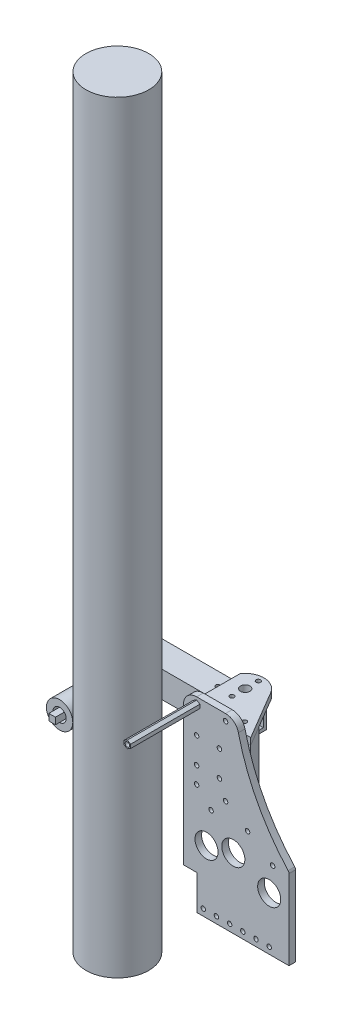
SolidWorks part; units mm, degrees
ref_plane "Front Plane" through (0, 0, 0) normal (0, 0, 1) x (1, 0, 0)
ref_plane "Top Plane" through (0, 0, 0) normal (0, 1, 0) x (1, 0, 0)
ref_plane "Right Plane" through (0, 0, 0) normal (1, 0, 0) x (0, 0, -1)
sketch "Elevation Bar" plane through (0, 0, 0) normal (0, 1, 0) x (1, 0, 0)
  circle A0 centre (0, 0) radius 30.226
  dimension "D1" = 60.452
extrude "Elevation Bar Part" add sketch "Elevation Bar" along normal blind 734.06
sketch "Pole and Drivetrain Pos" plane through (0, 0, 0) normal (0, 0, 1) x (1, 0, 0)
  line L0 (0, 0) -> (172.1794, 0) construction
  line L1 (-30.226, 0) -> (-30.226, 734.06) construction
  line L2 (-30.226, 734.06) -> (30.226, 734.06) construction
  line L3 (30.226, 734.06) -> (30.226, 0) construction
  line L4 (30.226, 0) -> (30.226, 734.06) construction
  line L5 (643.001, 41.275) -> (33.401, 41.275) construction
  line L6 (643.001, 53.975) -> (33.401, 53.975)
  line L7 (643.001, 53.975) -> (643.001, 28.575)
  line L8 (643.001, 28.575) -> (33.401, 28.575)
  line L9 (33.401, 53.975) -> (33.401, 28.575)
  line L10 (-30.226, 93.98) -> (30.226, 93.98) construction
  line L11 (33.2486, 0) -> (-33.2486, 0) construction
  line L12 (30.226, 185.42) -> (-30.226, 185.42) construction
  line L13 (30.226, 276.86) -> (-30.226, 276.86) construction
  line L14 (30.226, 368.3) -> (-30.226, 368.3) construction
  line L15 (30.226, 459.74) -> (-30.226, 459.74) construction
  line L16 (30.226, 551.18) -> (-30.226, 551.18) construction
  line L17 (30.226, 642.62) -> (-30.226, 642.62) construction
  line L18 (30.226, 73.152) -> (750.8896, 73.152) construction
  circle A0 centre (585.851, 41.275) radius 41.275 construction
  circle A1 centre (90.551, 41.275) radius 41.275 construction
  circle A2 centre (338.201, 41.275) radius 41.275 construction
  circle A3 centre (90.551, 41.275) radius 25.4
  point P24 (338.201, 41.275)
  point P28 (34.973, 41.275)
  dimension "D2" = 82.55
  dimension "D5" = 50.8
  dimension "D1" = 609.6
  dimension "D3" = 25.4
  dimension "D6" = 93.98
  dimension "D7" = 185.42
  dimension "D8" = 276.86
  dimension "D9" = 368.3
  dimension "D10" = 459.74
  dimension "D11" = 551.18
  dimension "D12" = 642.62
  dimension "D13" = 73.152
  dimension "D14" = 57.15
  dimension "D4" = 57.15
  dimension "D15" = 6.35
sketch "Driving Wheels Geo" plane through (0, 0, 0) normal (0, 0, 1) x (1, 0, 0)
  line L0 (-30.226, 182.88) -> (-30.226, 101.727) construction
  line L1 (55.626, 101.727) -> (30.226, 101.727) construction
  line L2 (-30.226, 0) -> (-30.226, 734.06) construction
  line L3 (30.226, 734.06) -> (30.226, 0) construction
  line L5 (30.226, 101.727) -> (-30.226, 101.727) construction
  line L6 (-30.226, 182.88) -> (30.226, 101.727) construction
  line L7 (31.8135, 101.727) -> (-30.226, 182.88) construction
  line L8 (30.226, 227.417) -> (203.668, 53.975) construction
  line L9 (-42.926, 195.58) -> (44.8729, 195.58) construction
  line L10 (30.226, 73.152) -> (750.8896, 73.152) construction
  line L11 (643.001, 53.975) -> (33.401, 53.975) construction
  line L14 (-42.926, 170.18) -> (44.8729, 170.18) construction
  line L15 (44.8729, 170.18) -> (44.8729, 195.58) construction
  line L16 (81.026, 28.575) -> (81.026, 257.175) construction
  line L17 (32.1729, 195.58) -> (57.5729, 195.58) construction
  line L18 (32.1729, 195.58) -> (32.1729, 170.18) construction
  line L19 (32.1729, 170.18) -> (57.5729, 170.18) construction
  line L20 (57.5729, 195.58) -> (57.5729, 170.18) construction
  line L21 (32.1729, 195.58) -> (57.5729, 170.18) construction
  line L22 (32.1729, 170.18) -> (57.5729, 195.58) construction
  line L23 (643.001, 28.575) -> (33.401, 28.575) construction
  line L24 (284.226, 257.175) -> (81.026, 257.175) construction
  line L25 (284.226, 257.175) -> (284.226, 53.975) construction
  line L26 (81.026, 257.175) -> (30.226, 257.175) construction
  circle A1 centre (55.626, 101.727) radius 25.4
  circle A3 centre (-42.926, 182.88) radius 12.7
  circle A4 centre (81.026, 104.775) radius 50.8 construction
  circle A5 centre (55.626, 101.727) radius 23.8125 construction
  circle A7 centre (284.226, 257.175) radius 203.2 construction
  point P28 (44.8729, 182.88)
  dimension "D1" = 50.8
  dimension "D2" = 1.5875
  dimension "D3" = 52.603
  dimension "D4" = 3.175
  dimension "D5" = 182.88
  dimension "D8" = 101.6
  dimension "D6" = 25.4
  dimension "D13" = 3.175
  dimension "D14" = 50.8
  dimension "D16" = 406.4
  dimension "D7" = 81.153
  dimension "D9" = 45
  dimension "D10" = 53.317
  dimension "D11" = 25.4
  dimension "D12" = 47.752
ref_plane "Plane1" through (0, 182.88, 0) normal (0, 1, 0) x (1, 0, 0)
sketch "Clamp Geo" plane through (0, 182.88, 0) normal (0, 1, 0) x (1, 0, 0)
  line L0 (-42.926, -19.8438) -> (-42.926, 87.3125) construction
  line L3 (33.401, 228.6) -> (33.401, -228.6) construction
  line L4 (56.3149, 61.9125) -> (-49.276, 61.9125)
  line L5 (56.3149, 61.9125) -> (56.3149, 87.3125)
  line L6 (56.3149, 87.3125) -> (-49.276, 87.3125)
  line L7 (-49.276, 61.9125) -> (-49.276, 87.3125)
  line L10 (-46.101, 87.3125) -> (-39.751, 87.3125)
  line L11 (-46.101, 87.3125) -> (-46.101, -19.8438)
  line L12 (-46.101, -19.8438) -> (-39.751, -19.8438)
  line L13 (-39.751, 87.3125) -> (-39.751, -19.8438)
  line L14 (-55.626, 12.7) -> (-30.226, 12.7) construction
  line L15 (-55.626, 12.7) -> (-55.626, -12.7) construction
  line L16 (-55.626, -12.7) -> (-30.226, -12.7) construction
  line L17 (-30.226, 12.7) -> (-30.226, -12.7) construction
  line L18 (-55.626, 12.7) -> (-30.226, -12.7) construction
  line L19 (-55.626, -12.7) -> (-30.226, 12.7) construction
  line L20 (0, -30.226) -> (0, 30.226) construction
  line L21 (-30.226, 0) -> (30.226, 0) construction
  line L22 (-46.101, 80.9625) -> (-42.926, 80.9625) construction
  line L23 (-39.751, 74.6125) -> (-46.101, 74.6125)
  line L24 (-46.101, 74.6125) -> (-46.101, 87.3125) construction
  line L25 (-39.751, 61.9125) -> (-39.751, 87.3125) construction
  line L26 (56.3149, 74.6125) -> (48.3774, 74.6125) construction
  line L27 (36.576, 57.1119) -> (36.576, 61.9125) construction
  line L28 (33.401, 61.9125) -> (39.751, 61.9125)
  line L29 (33.401, 61.9125) -> (33.401, 57.1119)
  line L30 (33.401, 57.1119) -> (39.751, 57.1119)
  line L31 (39.751, 61.9125) -> (39.751, 57.1119)
  circle A0 centre (0, 0) radius 30.226 construction
  circle A3 centre (-42.926, 80.9625) radius 1.8288
  circle A5 centre (-42.926, 68.2625) radius 1.8288
  circle A6 centre (48.3774, 74.6125) radius 4.7625
  circle A7 centre (48.3774, 74.6125) radius 14.9764 construction
  point P14 (-42.926, 0)
  point P32 (-39.751, 74.6125)
  point P34 (-46.101, 74.6125)
  point P36 (-42.926, 74.6125)
  point P42 (56.3149, 74.6125)
  point P50 (0, 0)
  dimension "D1" = 60.452
  dimension "D4" = 61.9125
  dimension "D7" = 3.6576
  dimension "D8" = 3.175
  dimension "D10" = 9.525
  dimension "D11" = 3.175
  dimension "D12" = 4.8006
  dimension "D2" = 457.2
  dimension "D3" = 25.4
  dimension "D5" = 6.35
  dimension "D6" = 25.4
  dimension "D9" = 105.5909
  dimension "D13" = 7.1437
  dimension "D14" = 6.35
extrude "Boss-Extrude1" add sketch "Clamp Geo" along normal blind 12.7 and the other way blind 12.7 separate body contours L6 L13 L4 L5 A6 | L11 L6 L7 L4 | L13 L23 L11 L4 A5 | L23 L13 L6 L11 A3 region at (7.0759, 182.88, -74.6125) region at (-39.893, 182.88, -80.9625) region at (-42.926, 182.88, -62.0545) region at (-47.6885, 182.88, -74.6125)
sketch "Locked Setting Geo" plane through (0, 182.88, 0) normal (0, 1, 0) x (1, 0, 0)
  line L0 (37.1358, 206.7277) -> (116.0692, 134.2573) construction
  line L1 (34.9193, 74.038) -> (106.3312, 151.8184)
  line L2 (34.9193, 74.038) -> (48.9519, 61.1544)
  line L3 (48.9519, 61.1544) -> (120.3638, 138.9348)
  line L4 (106.3312, 151.8184) -> (120.3638, 138.9348)
  line L5 (118.2165, 136.596) -> (113.922, 131.9185)
  line L6 (118.2165, 136.596) -> (39.283, 209.0665)
  line L7 (39.283, 209.0665) -> (34.9885, 204.389)
  line L8 (113.922, 131.9185) -> (34.9885, 204.389)
  line L9 (72.036, 191.926) -> (54.8578, 173.2158) construction
  line L10 (72.036, 191.926) -> (53.3259, 209.1042) construction
  line L11 (53.3259, 209.1042) -> (36.1477, 190.394) construction
  line L12 (54.8578, 173.2158) -> (36.1477, 190.394) construction
  line L13 (72.036, 191.926) -> (36.1477, 190.394) construction
  line L14 (53.3259, 209.1042) -> (54.8578, 173.2158) construction
  line L15 (39.751, 61.9125) -> (39.751, 57.1119) construction
  line L16 (47.1953, 87.4087) -> (28.4851, 104.5869)
  line L17 (114.7084, 139.8169) -> (112.5611, 137.4782) construction
  line L18 (106.9057, 138.3603) -> (111.2002, 143.0379)
  line L19 (111.2002, 143.0379) -> (118.2165, 136.596) construction
  line L20 (99.8893, 144.8021) -> (113.922, 131.9185) construction
  line L21 (41.9356, 67.5962) -> (48.3774, 74.6125) construction
  line L22 (56.3149, 87.3125) -> (-49.276, 87.3125) construction
  line L23 (-46.101, 87.3125) -> (-46.101, -19.8438) construction
  line L24 (33.401, 228.6) -> (33.401, -228.6) construction
  line L25 (28.4851, 104.5869) -> (32.7797, 109.2645)
  line L26 (32.7797, 109.2645) -> (51.4898, 92.0863)
  circle A1 centre (112.5611, 137.4782) radius 1.8288
  circle A2 centre (105.5448, 143.92) radius 1.8288
  circle A3 centre (48.3774, 74.6125) radius 6.35
  point P0 (-42.926, 74.6125)
  point P9 (-42.926, 0)
  point P10 (54.0919, 191.16)
  point P28 (106.9057, 138.3603)
  point P30 (111.2002, 143.0379)
  point P32 (109.0529, 140.6991)
  point P36 (41.9356, 67.5962)
  point P40 (48.3774, 74.6125)
  dimension "D15" = 6.35
  dimension "D6" = 3.6576
  dimension "D9" = 12.7
  dimension "D2" = 19.05
  dimension "D4" = 6.35
  dimension "D5" = 25.4
  dimension "D7" = 3.175
  dimension "D8" = 105.5909
  dimension "D10" = 3.175
  dimension "D3" = 1.5875
  dimension "D12" = 86.9628
  dimension "D11" = 74.6125
  dimension "D13" = 74.6125
  dimension "D14" = 8.6264
  dimension "D16" = 25.4
  dimension "D17" = 8.6264
sketch "Sketch2" plane through (-49.276, 0, 0) normal (-1, 0, 0) x (0, 0, 1)
  line L0 (-74.6125, 195.58) -> (-74.6125, 170.18) construction
  line L1 (-61.9125, 195.58) -> (-87.3125, 195.58) construction
  line L2 (-61.9125, 170.18) -> (-87.3125, 170.18) construction
  line L3 (-61.9125, 170.18) -> (-61.9125, 195.58) construction
  line L4 (-84.1375, 173.355) -> (-65.0875, 173.355)
  line L5 (-84.1375, 173.355) -> (-84.1375, 192.405)
  line L6 (-84.1375, 192.405) -> (-65.0875, 192.405)
  line L7 (-65.0875, 173.355) -> (-65.0875, 192.405)
  line L8 (-84.1375, 173.355) -> (-65.0875, 192.405) construction
  line L9 (-84.1375, 192.405) -> (-65.0875, 173.355) construction
  point P6 (-74.6125, 182.88)
  dimension "D1" = 3.175
  dimension "D2" = 3.175
extrude "Cut-Extrude2" cut sketch "Sketch2" against normal up to surface (105.5909 mm away) up to face at (56.3149, 182.88, -74.6125)
sketch "Sketch3" plane through (0, 0, -87.3125) normal (0, 0, -1) x (-1, 0, 0)
  line L2 (39.7129, 179.6669) -> (46.1391, 179.6669) construction
  line L3 (39.7129, 179.6669) -> (39.7129, 186.0931) construction
  line L4 (39.7129, 186.0931) -> (46.1391, 186.0931) construction
  line L5 (46.1391, 179.6669) -> (46.1391, 186.0931) construction
  line L6 (39.7129, 179.6669) -> (46.1391, 186.0931) construction
  line L7 (39.7129, 186.0931) -> (46.1391, 179.6669) construction
  circle A1 centre (42.926, 182.88) radius 4.544
  point P0 (42.926, 182.88)
  point P1 (42.926, 182.88)
  dimension "D1" = 6.4262
extrude "Cut-Extrude3" cut sketch "Sketch3" against normal up to surface (25.4 mm away) up to face at (3.5195, 182.88, -61.9125)
extrude "Boss-Extrude2" add sketch "Clamp Geo<3>" along normal blind 3.175 and the other way blind 3.175 separate body contours L13 L4 L11 L12 | L13 L23 L11 L4 A5 | L23 L13 L6 L11 A3 region at (-39.893, 182.88, -80.9625) region at (-42.926, 182.88, -21.0344) region at (-42.926, 182.88, -62.0545)
sketch "Clamp Geo<3>" plane through (0, 182.88, 0) normal (0, 1, 0) x (1, 0, 0) same geometry as "Clamp Geo"
sketch "Custom Driven Flywheel" plane through (0, 0, 0) normal (0, 0, 1) x (1, 0, 0)
  circle A0 centre (-42.926, 182.88) radius 12.7 construction
  circle A1 centre (-42.926, 182.88) radius 12.7
  circle A2 centre (-42.926, 182.88) radius 6.35
  dimension "D1" = 12.7
extrude "Boss-Extrude3" add sketch "Custom Driven Flywheel" along normal blind 12.7 and the other way blind 25.4 separate body
sketch "Sketch8" plane through (0, 173.355, 0) normal (0, 1, 0) x (1, 0, 0)
  line L0 (-42.926, 84.1375) -> (-42.926, 65.0875) construction
  line L5 (-36.576, 74.6125) -> (-42.926, 74.6125) construction
  line L6 (-42.926, 74.6125) -> (-49.276, 74.6125) construction
  line L11 (56.3149, 65.0875) -> (-49.276, 65.0875) construction
  line L12 (56.3149, 84.1375) -> (-49.276, 84.1375) construction
  line L13 (56.3149, 65.0875) -> (-49.276, 65.0875) construction
  line L14 (56.3149, 84.1375) -> (-49.276, 84.1375) construction
  line L15 (-49.276, 84.1375) -> (-49.276, 65.0875) construction
  line L17 (-49.276, 65.3415) -> (-36.576, 65.3415)
  line L18 (-49.276, 65.3415) -> (-49.276, 83.8835)
  line L19 (-49.276, 83.8835) -> (-36.576, 83.8835)
  line L20 (-36.576, 65.3415) -> (-36.576, 83.8835)
  line L21 (-49.276, 65.3415) -> (-36.576, 83.8835) construction
  line L22 (-49.276, 83.8835) -> (-36.576, 65.3415) construction
  circle A0 centre (-42.926, 80.9625) radius 1.8288 construction
  circle A1 centre (-42.926, 80.9625) radius 1.8288 construction
  circle A2 centre (-42.926, 68.2625) radius 1.8288 construction
  circle A3 centre (-42.926, 80.9625) radius 1.8288
  circle A4 centre (-42.926, 68.2625) radius 1.8288
  dimension "D1" = 0.254
extrude "Boss-Extrude5" add sketch "Sketch8" along normal up to surface (9.525 mm away) separate body up to plane "Plane1"
sketch "Sketch10" plane through (0, 182.88, 0) normal (0, 1, 0) x (1, 0, 0)
  line L0 (-36.576, 83.8835) -> (-49.276, 83.8835) construction
  line L8 (-39.751, 65.3415) -> (-46.101, 65.3415)
  line L9 (-39.751, 65.3415) -> (-39.751, 83.8835)
  line L10 (-39.751, 83.8835) -> (-46.101, 83.8835)
  line L11 (-46.101, 65.3415) -> (-46.101, 83.8835)
  line L12 (-39.751, 65.3415) -> (-46.101, 83.8835) construction
  line L13 (-39.751, 83.8835) -> (-46.101, 65.3415) construction
  circle A0 centre (-42.926, 68.2625) radius 1.8288 construction
  circle A1 centre (-42.926, 80.9625) radius 1.8288 construction
  circle A2 centre (-42.926, 68.2625) radius 1.8288
  circle A3 centre (-42.926, 80.9625) radius 1.8288
  point P0 (-42.926, 74.6125)
  dimension "D1" = 6.35
extrude "Cut-Extrude5" cut sketch "Sketch10" against normal blind 3.175
ref_plane "Plane2" through (0, 0, 210.82) normal (0, 0, 1) x (1, 0, 0)
ref_plane "Plane3" through (0, 0, 166.37) normal (0, 0, 1) x (1, 0, 0)
sketch "Sketch12" plane through (0, 0, 166.37) normal (0, 0, 1) x (1, 0, 0)
  line L0 (643.001, 41.275) -> (33.401, 41.275) construction
  line L1 (643.001, 41.275) -> (33.401, 41.275) construction
  line L2 (90.551, 41.275) -> (103.251, 41.275) construction
  line L3 (115.951, 41.275) -> (115.951, 92.4703) construction
  circle A0 centre (90.551, 41.275) radius 25.4 construction
  circle A1 centre (90.551, 41.275) radius 25.4
  circle A2 centre (55.626, 101.727) radius 17.78
  circle A4 centre (81.4092, 108.5474) radius 8.89
  circle A5 centre (135.001, 41.275) radius 19.05
  circle A7 centre (81.4092, 108.5474) radius 25.4
  circle A8 centre (115.951, 92.4703) radius 12.7
  circle A9 centre (115.951, 92.4703) radius 31.75
  circle A10 centre (90.551, 41.275) radius 3.175 construction
  circle A11 centre (103.251, 41.275) radius 3.175 construction
  circle A12 centre (115.951, 41.275) radius 3.175 construction
  circle A13 centre (128.651, 41.275) radius 3.175 construction
  circle A14 centre (141.351, 41.275) radius 3.175 construction
  circle A15 centre (154.051, 41.275) radius 3.175 construction
  circle A16 centre (166.751, 41.275) radius 3.175 construction
  circle A17 centre (179.451, 41.275) radius 3.175 construction
  circle A18 centre (192.151, 41.275) radius 3.175 construction
  circle A19 centre (204.851, 41.275) radius 3.175 construction
  point P0 (78.4034, 98.9347)
  point P3 (55.626, 101.727)
  dimension "D2" = 17.78
  dimension "D3" = 63.5
  dimension "D4" = 38.1
  dimension "D5" = 50.8
  dimension "D6" = 25.4
  dimension "D7" = 35.56
  dimension "D8" = 6.35
  dimension "D10" = 12.7
  dimension "D9" = 10
sketch "Sketch13" plane through (0, 0, 210.82) normal (0, 0, 1) x (1, 0, 0)
  line L0 (115.951, 79.7703) -> (115.951, 105.1703) construction
  line L2 (96.901, 79.7703) -> (96.901, 105.1703)
  line L4 (160.401, 79.7703) -> (160.401, 105.1703)
  line L5 (154.051, 92.4703) -> (154.051, 41.275) construction
  line L6 (115.951, 92.4703) -> (160.401, 92.4703) construction
  line L7 (96.901, 92.4703) -> (115.951, 92.4703) construction
  line L8 (96.901, 105.1703) -> (115.951, 105.1703)
  line L9 (96.901, 79.7703) -> (115.951, 79.7703)
  line L10 (115.951, 105.1703) -> (160.401, 105.1703)
  line L11 (160.401, 79.7703) -> (115.951, 79.7703)
  circle A0 centre (115.951, 92.4703) radius 3.175 construction
  circle A1 centre (103.251, 92.4703) radius 3.175 construction
  circle A2 centre (154.051, 92.4703) radius 3.175 construction
  point P0 (115.951, 92.4703)
  dimension "D2" = 6.35
  dimension "D3" = 6.35
  dimension "D6" = 6.35
  dimension "D1" = 25.4
  dimension "D4" = 12.7
  dimension "D5" = 6.35
ref_plane "Plane5" through (0, 0, 146.177) normal (0, 0, 1) x (1, 0, 0)
sketch "Sketch15" plane through (0, 0, 146.177) normal (0, 0, 1) x (1, 0, 0)
  line L0 (96.901, 79.7703) -> (115.951, 79.7703) construction
  line L1 (160.401, 79.7703) -> (115.951, 79.7703) construction
  line L2 (160.401, 79.7703) -> (160.401, 105.1703) construction
  line L3 (115.951, 105.1703) -> (160.401, 105.1703) construction
  line L4 (96.901, 105.1703) -> (115.951, 105.1703) construction
  line L5 (96.901, 79.7703) -> (96.901, 105.1703) construction
  line L6 (96.901, 79.7703) -> (115.951, 79.7703)
  line L7 (160.401, 79.7703) -> (115.951, 79.7703)
  line L8 (160.401, 79.7703) -> (160.401, 105.1703)
  line L9 (115.951, 105.1703) -> (160.401, 105.1703)
  line L10 (96.901, 105.1703) -> (115.951, 105.1703)
  line L11 (96.901, 79.7703) -> (96.901, 105.1703)
  line L12 (96.901, 28.575) -> (115.951, 28.575)
  line L13 (160.401, 28.575) -> (115.951, 28.575)
  line L14 (160.401, 28.575) -> (160.401, 53.975)
  line L15 (115.951, 53.975) -> (160.401, 53.975)
  line L16 (96.901, 53.975) -> (115.951, 53.975)
  line L17 (96.901, 28.575) -> (96.901, 53.975)
  line L18 (160.401, 28.575) -> (96.901, 53.975) construction
  line L19 (115.951, 53.975) -> (115.951, 28.575) construction
  line L20 (160.401, 41.275) -> (96.901, 41.275) construction
  circle A0 centre (115.951, 92.4703) radius 3.175 construction
  circle A1 centre (115.951, 92.4703) radius 3.175
  circle A2 centre (115.951, 41.275) radius 3.175 construction
  dimension "D5" = 6.35
  dimension "D1" = 68.3916
  dimension "D2" = 68.3916
  dimension "D3" = 19.05
  dimension "D4" = 25.4
ref_plane "Plane6" through (0, 53.975, 0) normal (0, 1, 0) x (1, 0, 0)
ref_plane "Plane9" through (0, 74.6125, 0) normal (0, 1, 0) x (1, 0, 0)
sketch "Sketch16" plane through (0, 74.6125, 0) normal (0, 1, 0) x (1, 0, 0)
  line L0 (33.401, -127) -> (33.401, 127)
  line L1 (39.751, 120.65) -> (39.751, 107.95) construction
  line L2 (33.401, 127) -> (46.101, 127)
  line L3 (33.401, 127) -> (33.401, -127)
  line L4 (33.401, -127) -> (46.101, -127)
  line L5 (46.101, 127) -> (46.101, -127)
  line L6 (39.751, 120.65) -> (39.751, 127) construction
  line L7 (141.351, -166.37) -> (141.351, -127) construction
  line L8 (643.001, 0) -> (33.401, 0) construction
  line L9 (135.001, 127) -> (147.701, 127)
  line L14 (135.001, 127) -> (135.001, -127)
  line L15 (135.001, -127) -> (147.701, -127)
  line L16 (147.701, 127) -> (147.701, -127)
  line L17 (135.001, 127) -> (147.701, -127) construction
  line L18 (135.001, -127) -> (147.701, 127) construction
  line L19 (141.351, -120.65) -> (141.351, -107.95) construction
  line L20 (141.351, -127) -> (141.351, -120.65) construction
  circle A0 centre (39.751, 120.65) radius 3.175
  circle A1 centre (39.751, 107.95) radius 3.175
  circle A2 centre (39.751, 95.25) radius 3.175
  circle A3 centre (39.751, 82.55) radius 3.175
  circle A4 centre (39.751, 69.85) radius 3.175
  circle A5 centre (39.751, 57.15) radius 3.175
  circle A6 centre (39.751, 44.45) radius 3.175
  circle A7 centre (39.751, 31.75) radius 3.175
  circle A8 centre (39.751, 19.05) radius 3.175
  circle A9 centre (39.751, 6.35) radius 3.175
  circle A10 centre (39.751, -6.35) radius 3.175
  circle A11 centre (39.751, -19.05) radius 3.175
  circle A12 centre (39.751, -31.75) radius 3.175
  circle A13 centre (39.751, -44.45) radius 3.175
  circle A14 centre (39.751, -57.15) radius 3.175
  circle A15 centre (39.751, -69.85) radius 3.175
  circle A16 centre (39.751, -82.55) radius 3.175
  circle A17 centre (39.751, -95.25) radius 3.175
  circle A18 centre (39.751, -107.95) radius 3.175
  circle A19 centre (39.751, -120.65) radius 3.175
  circle A40 centre (141.351, -120.65) radius 3.175
  circle A41 centre (141.351, -107.95) radius 3.175
  circle A42 centre (141.351, -95.25) radius 3.175
  circle A43 centre (141.351, -82.55) radius 3.175
  circle A44 centre (141.351, -69.85) radius 3.175
  circle A45 centre (141.351, -57.15) radius 3.175
  circle A46 centre (141.351, -44.45) radius 3.175
  circle A47 centre (141.351, -31.75) radius 3.175
  circle A48 centre (141.351, -19.05) radius 3.175
  circle A49 centre (141.351, -6.35) radius 3.175
  circle A50 centre (141.351, 6.35) radius 3.175
  circle A51 centre (141.351, 19.05) radius 3.175
  circle A52 centre (141.351, 31.75) radius 3.175
  circle A53 centre (141.351, 44.45) radius 3.175
  circle A54 centre (141.351, 57.15) radius 3.175
  circle A55 centre (141.351, 69.85) radius 3.175
  circle A56 centre (141.351, 82.55) radius 3.175
  circle A57 centre (141.351, 95.25) radius 3.175
  circle A58 centre (141.351, 107.95) radius 3.175
  circle A59 centre (141.351, 120.65) radius 3.175
  point P3 (33.401, 0)
  point P9 (141.351, -166.37)
  point P51 (141.351, 0)
  point P60 (0, 0)
  dimension "D3" = 6.35
  dimension "D1" = 254
  dimension "D2" = 12.7
  dimension "D4" = 6.35
  dimension "D6" = 12.7
  dimension "D10" = 6.35
  dimension "D12" = 12.7
  dimension "D5" = 20
  dimension "D11" = 20
sketch "Sketch18" plane through (0, 53.975, 0) normal (0, 1, 0) x (1, 0, 0)
  line L0 (33.401, -36.5125) -> (147.701, -36.5125)
  line L3 (643.001, 0) -> (33.401, 0) construction
  line L4 (33.401, -49.2125) -> (147.701, -49.2125)
  line L5 (33.401, -36.5125) -> (33.401, -49.2125)
  line L6 (147.701, -36.5125) -> (147.701, -49.2125)
  line L7 (33.401, -42.8625) -> (147.701, -42.8625) construction
  line L8 (39.751, -42.8625) -> (52.451, -42.8625) construction
  line L9 (-403.733, 0) -> (403.733, 0) construction
  line L10 (39.751, 42.8625) -> (52.451, 42.8625) construction
  line L11 (33.401, 42.8625) -> (147.701, 42.8625) construction
  line L12 (147.701, 36.5125) -> (147.701, 49.2125)
  line L13 (33.401, 36.5125) -> (33.401, 49.2125)
  line L14 (33.401, 49.2125) -> (147.701, 49.2125)
  line L15 (33.401, 36.5125) -> (147.701, 36.5125)
  line L16 (33.401, 228.6) -> (33.401, -228.6) construction
  line L17 (147.701, 127) -> (147.701, -127) construction
  circle A0 centre (39.751, -42.8625) radius 3.175
  circle A1 centre (52.451, -42.8625) radius 3.175
  circle A2 centre (65.151, -42.8625) radius 3.175
  circle A3 centre (77.851, -42.8625) radius 3.175
  circle A4 centre (90.551, -42.8625) radius 3.175
  circle A5 centre (103.251, -42.8625) radius 3.175
  circle A6 centre (115.951, -42.8625) radius 3.175
  circle A7 centre (115.951, 42.8625) radius 3.175
  circle A8 centre (103.251, 42.8625) radius 3.175
  circle A9 centre (90.551, 42.8625) radius 3.175
  circle A10 centre (77.851, 42.8625) radius 3.175
  circle A11 centre (65.151, 42.8625) radius 3.175
  circle A12 centre (52.451, 42.8625) radius 3.175
  circle A13 centre (39.751, 42.8625) radius 3.175
  circle A14 centre (128.651, -42.8625) radius 3.175
  circle A15 centre (141.351, -42.8625) radius 3.175
  dimension "D4" = 6.35
  dimension "D1" = 36.5125
  dimension "D2" = 12.7
  dimension "D3" = 6.35
  dimension "D6" = 12.7
  dimension "D8" = 12.7
  dimension "D5" = 7
  dimension "D7" = 3
ref_plane "Plane7" through (0, 0, -36.5125) normal (0, 0, 1) x (1, 0, 0)
sketch "Sketch17" plane through (0, 0, -36.5125) normal (0, 0, 1) x (1, 0, 0)
  line L2 (135.001, 118.0172) -> (135.001, 73.152)
  line L9 (33.401, 53.975) -> (147.701, 53.975) construction
  line L10 (46.355, 74.6125) -> (46.355, 41.275)
  line L11 (46.355, 41.275) -> (135.001, 41.275)
  line L13 (135.001, 73.152) -> (135.001, 41.275)
  line L14 (55.626, 101.727) -> (55.626, 41.275) construction
  line L15 (46.101, 214.63) -> (46.101, 147.955) construction
  line L17 (33.401, 74.6125) -> (33.401, 208.28)
  line L20 (46.355, 74.6125) -> (33.401, 74.6125)
  line L23 (46.101, 220.98) -> (46.101, 214.63) construction
  line L24 (46.101, 214.63) -> (73.9355, 214.63) construction
  line L25 (73.9355, 220.98) -> (73.9355, 214.63) construction
  line L27 (33.401, 160.02) -> (33.401, 136.2126) construction
  line L30 (56.3149, 170.18) -> (-49.276, 170.18) construction
  line L31 (73.9355, 214.63) -> (73.9355, 147.955) construction
  line L32 (46.101, 147.955) -> (73.9355, 147.955) construction
  line L33 (81.4092, 108.5474) -> (134.1706, 120.1581) construction
  line L35 (46.101, 220.98) -> (73.9355, 220.98)
  line L36 (60.0183, 214.63) -> (60.0183, 220.98) construction
  line L37 (56.3149, 195.58) -> (-49.276, 195.58) construction
  line L38 (60.0183, 147.955) -> (60.0183, 118.9559) construction
  line L39 (73.9355, 147.955) -> (119.2867, 116.8828) construction
  circle A0 centre (55.626, 101.727) radius 11.1125
  circle A1 centre (81.4092, 108.5474) radius 11.1125
  circle A2 centre (115.951, 92.4703) radius 11.1125
  circle A6 centre (284.226, 257.175) radius 203.2 construction
  arc A7 (86.3055, 211.1562) -> (134.1706, 120.1581) centre (284.226, 257.175) ccw
  arc A9 (135.001, 118.0172) -> (134.1706, 120.1581) centre (131.826, 118.0172) ccw
  arc A10 (86.3055, 211.1562) -> (73.9355, 220.98) centre (73.9355, 208.28) ccw
  arc A11 (33.401, 208.28) -> (46.101, 220.98) centre (46.101, 208.28) cw
  circle A12 centre (46.101, 214.63) radius 2.1527
  circle A13 centre (73.9355, 214.63) radius 2.1527
  circle A21 centre (119.2867, 116.8828) radius 2.1527
  circle A23 centre (46.101, 147.955) radius 2.1527
  circle A24 centre (73.9355, 147.955) radius 2.1527
  circle A25 centre (55.626, 101.727) radius 17.78 construction
  circle A26 centre (60.0183, 133.4555) radius 2.1527
  circle A27 centre (95.0982, 133.4555) radius 2.1526
  point P22 (0, 0)
  point P25 (135.001, 119.2542)
  point P26 (0, 0)
  point P27 (0, 0)
  point P33 (134.6729, 73.152)
  point P55 (0, 0)
  point P56 (33.3012, 75.6194)
  point P57 (33.4967, 72.7702)
  point P58 (33.5821, 75.0431)
  point P59 (33.7233, 74.0007)
  point P60 (33.702, 73.7674)
  point P61 (0, 0)
  point P62 (46.101, 147.955)
  point P65 (91.2977, 135.194)
  point P66 (0, 0)
  point P70 (135.8375, 41.275)
  dimension "D1" = 22.225
  dimension "D2" = 25.4
  dimension "D6" = 12.7
  dimension "D7" = 3.175
  dimension "D9" = 4.3053
  dimension "D13" = 15.24
  dimension "D3" = 12.954
  dimension "D4" = 12.7
  dimension "D5" = 88.646
  dimension "D8" = 6.35
  dimension "D10" = 22.225
extrude "Boss-Extrude6" add sketch "Sketch17" along normal blind 6.35 separate body
sketch "Sketch19" plane through (0, 0, 0) normal (0, 0, 1) x (1, 0, 0)
  line L0 (39.751, 47.625) -> (115.951, 47.625) construction
  line L1 (39.751, 41.275) -> (39.751, 53.975) construction
  line L2 (643.001, 41.275) -> (33.401, 41.275) construction
  line L3 (643.001, 53.975) -> (33.401, 53.975) construction
  line L4 (39.751, 47.625) -> (52.451, 47.625) construction
  circle A0 centre (39.751, 47.625) radius 2.1527
  circle A1 centre (52.451, 47.625) radius 2.1527
  circle A2 centre (65.151, 47.625) radius 2.1527
  circle A3 centre (77.851, 47.625) radius 2.1527
  circle A4 centre (90.551, 47.625) radius 2.1527
  circle A5 centre (103.251, 47.625) radius 2.1527
  circle A6 centre (115.951, 47.625) radius 2.1527
  dimension "D2" = 4.3053
  dimension "D1" = 6.35
  dimension "D4" = 12.7
  dimension "D3" = 7
sketch "Sketch22" plane through (0, 53.975, 0) normal (0, 1, 0) x (1, 0, 0)
  line L0 (-52.7651, -82.55) -> (244.2686, -82.55) construction
  line L1 (-403.733, 0) -> (403.733, 0) construction
  line L2 (-52.7651, 82.55) -> (244.2686, 82.55) construction
  dimension "D1" = 165.1
extrude "Cut-Extrude6" cut sketch "Sketch19" against normal up to surface (36.5125 mm away) up to face at (97.2508, 133.4555, -36.5125)
ref_plane "Plane8" through (0, 200.3425, 0) normal (0, 1, 0) x (1, 0, 0)
sketch "Sketch23" plane through (0, 200.3425, 0) normal (0, 1, 0) x (1, 0, 0)
  line L0 (33.401, 84.6476) -> (33.401, 36.5125)
  line L1 (54.6037, 36.5125) -> (50.2984, 36.5125) construction
  line L2 (33.401, 36.5125) -> (91.821, 36.5125)
  line L3 (91.821, 36.5125) -> (63.8994, 83.7813)
  line L4 (33.401, 57.0961) -> (79.6623, 57.0961) construction
  line L5 (56.5317, 57.0961) -> (56.5317, 36.5125) construction
  line L6 (86.3055, 36.5125) -> (134.1706, 36.5125) construction
  line L7 (56.5317, 46.8043) -> (33.401, 46.8043) construction
  line L8 (35.2696, 74.6125) -> (48.4608, 74.6125) construction
  line L9 (56.5317, 46.8043) -> (75.5817, 46.8043) construction
  line L10 (48.3774, 74.6125) -> (48.3774, 87.3125) construction
  line L11 (33.401, 228.6) -> (33.401, -228.6) construction
  circle A0 centre (48.3774, 74.6125) radius 14.9764 construction
  circle A4 centre (56.5317, 46.8043) radius 2.1527
  circle A7 centre (48.3774, 74.6125) radius 4.5466
  circle A8 centre (75.5817, 46.8043) radius 2.1527
  circle A9 centre (48.3774, 87.3125) radius 2.1527
  circle A10 centre (48.3774, 61.9125) radius 2.1527
  arc A11 (33.401, 64.5774) -> (33.401, 84.6476) centre (48.3774, 74.6125) ccw
  point P27 (62.8176, 83.2089)
  point P28 (0, 0)
  point P29 (0, 0)
  point P32 (27.051, 84.5816)
  dimension "D4" = 4.3053
  dimension "D3" = 9.0932
  dimension "D2" = 2.54
  dimension "D6" = 4.3053
  dimension "D8" = 3.175
  dimension "D1" = 58.42
  dimension "D5" = 19.05
  dimension "D7" = 12.7
extrude "Boss-Extrude7" add sketch "Sketch23" along normal blind 6.35 separate body contours A11 L0 L2 L3 A4 | A11 L0 | A11 | A11 | A11 | A11 region at (48.8754, 200.3425, -92.1443) region at (60.4886, 200.3425, -49.5269)
sketch "Sketch25" plane through (0, 200.3425, 0) normal (0, -1, 0) x (1, 0, 0)
  line L0 (91.821, -36.5125) -> (63.8994, -83.7813) construction
  line L1 (33.401, -36.5125) -> (91.821, -36.5125) construction
  line L2 (33.401, -84.6476) -> (33.401, -36.5125) construction
  line L3 (33.401, -57.0961) -> (79.6623, -57.0961) construction
  line L4 (91.821, -36.5125) -> (80.3996, -55.8479)
  line L5 (33.401, -36.5125) -> (91.821, -36.5125)
  line L6 (33.401, -54.5561) -> (33.401, -36.5125)
  line L7 (35.941, -57.0961) -> (78.2126, -57.0961)
  circle A0 centre (56.5317, -46.8043) radius 2.1526 construction
  circle A2 centre (56.5317, -46.8043) radius 2.1527
  arc A4 (78.2126, -57.0961) -> (80.3996, -55.8479) centre (78.2126, -54.5561) ccw
  arc A5 (35.941, -57.0961) -> (33.401, -54.5561) centre (35.941, -54.5561) cw
  circle A6 centre (75.5817, -46.8043) radius 2.1527 construction
  circle A7 centre (75.5817, -46.8043) radius 2.1527
  dimension "D1" = 2.54
extrude "Boss-Extrude8" add sketch "Sketch25" along normal blind 47.879 separate body
sketch "Sketch26" plane through (0, 0, -57.0961) normal (0, 0, -1) x (-1, 0, 0)
  line L0 (-78.2126, 200.3425) -> (-35.941, 152.4635) construction
  line L1 (-78.2126, 152.4635) -> (-35.941, 200.3425) construction
  line L3 (-68.0526, 163.9712) -> (-46.101, 163.9712) construction
  line L4 (-35.941, 200.3425) -> (-78.2126, 200.3425)
  line L5 (-78.2126, 200.3425) -> (-78.2126, 152.4635)
  line L6 (-78.2126, 152.4635) -> (-35.941, 152.4635)
  line L7 (-35.941, 152.4635) -> (-35.941, 200.3425)
  line L9 (-78.2126, 200.3425) -> (-78.2126, 152.4635) construction
  line L10 (-78.2126, 152.4635) -> (-35.941, 152.4635) construction
  line L11 (-35.941, 152.4635) -> (-35.941, 200.3425) construction
  line L12 (-68.0526, 163.9712) -> (-68.0526, 188.8348) construction
  line L13 (-68.0526, 188.8348) -> (-46.101, 188.8348) construction
  line L14 (-46.101, 163.9712) -> (-46.101, 188.8348) construction
  line L15 (-68.0526, 163.9712) -> (-46.101, 188.8348) construction
  line L16 (-68.0526, 188.8348) -> (-46.101, 163.9712) construction
  line L20 (-35.941, 200.3425) -> (-78.2126, 200.3425)
  circle A1 centre (-68.0526, 163.9712) radius 2.1527
  circle A2 centre (-46.101, 163.9712) radius 2.1527
  circle A3 centre (-68.0526, 188.8348) radius 2.1527
  circle A4 centre (-46.101, 188.8348) radius 2.1527
  point P2 (-57.0768, 176.403)
  dimension "D3" = 4.3053
  dimension "D2" = 10.16
  dimension "D1" = 0
extrude "Cut-Extrude8" cut sketch "Sketch26" against normal up to surface (26.9336 mm away) contours A3 | A1 | A2 | A4 region at (68.0526, 163.9712, -57.0961) region at (46.101, 163.9712, -57.0961) region at (68.0526, 188.8348, -57.0961) region at (46.101, 188.8348, -57.0961) up to face at (50.2984, 47.625, -30.1625)
sketch "Sketch27" plane through (0, 0, -30.1625) normal (0, 0, 1) x (1, 0, 0)
  line L0 (42.926, 216.4631) -> (42.926, 212.7969)
  line L1 (46.101, 218.2962) -> (42.926, 216.4631)
  line L2 (49.276, 216.4631) -> (46.101, 218.2962)
  line L3 (49.276, 212.7969) -> (49.276, 216.4631)
  line L4 (46.101, 210.9638) -> (49.276, 212.7969)
  line L5 (42.926, 212.7969) -> (46.101, 210.9638)
  circle A0 centre (46.101, 214.63) radius 3.175 construction
  circle A1 centre (46.101, 214.63) radius 2.1526 construction
  circle A2 centre (46.101, 214.63) radius 2.1527
  point P16 (39.751, 208.28)
  point P20 (46.101, 214.63)
  dimension "D1" = 6.35
  dimension "D3" = 6
extrude "Boss-Extrude9" add sketch "Sketch27" along normal up to vertex (66.675 mm away) separate body up to point (33.401, 53.975, 36.5125)
sketch "Sketch28" plane through (0, 0, -61.9125) normal (0, 0, 1) x (1, 0, 0)
  line L0 (36.576, 195.58) -> (36.576, 170.18) construction
  line L1 (56.3149, 195.58) -> (-49.276, 195.58) construction
  line L2 (56.3149, 170.18) -> (-49.276, 170.18) construction
  line L4 (33.401, 184.7131) -> (33.401, 181.0469)
  line L5 (36.576, 182.88) -> (33.401, 182.88) construction
  line L6 (36.576, 186.5462) -> (33.401, 184.7131)
  line L7 (39.751, 184.7131) -> (36.576, 186.5462)
  line L8 (39.751, 181.0469) -> (39.751, 184.7131)
  line L9 (36.576, 179.2138) -> (39.751, 181.0469)
  line L10 (33.401, 181.0469) -> (36.576, 179.2138)
  circle A0 centre (36.576, 182.88) radius 2.1527
  circle A1 centre (36.576, 182.88) radius 3.175 construction
  point P27 (36.576, 182.88)
  dimension "D1" = 4.3053
  dimension "D3" = 6.35
  dimension "D4" = 6
extrude "Boss-Extrude10" add sketch "Sketch28" along normal up to vertex (4.8006 mm away) separate body up to point (33.401, 182.88, -57.1119)
sketch "Sketch31" plane through (0, 0, -61.9125) normal (0, 0, 1) x (1, 0, 0)
  circle A0 centre (36.576, 182.88) radius 2.1527 construction
  circle A1 centre (36.576, 182.88) radius 2.1527
extrude "Cut-Extrude9" cut sketch "Sketch31" against normal up to surface (25.4 mm away) up to face at (-47.47, 182.88, -87.3125)
sketch "Sketch32" [suppressed] plane through (0, 0, -36.5125) normal (0, 0, -1) x (-1, 0, 0)
  line L0 (14.224, 182.88) -> (7.874, 182.88) construction
  line L1 (14.224, 182.88) -> (7.874, 182.88) construction
  line L2 (10.7449, 188.5957) -> (16.442, 180.9623) construction
  line L3 (16.442, 180.9623) -> (-44.0579, 135.8088) construction
  line L4 (-44.0579, 135.8088) -> (-42.9249, 60.325) construction
  line L5 (-42.9249, 60.325) -> (-33.401, 60.4679) construction
  line L6 (-44.0579, 135.8088) -> (-44.446, 161.6666) construction
  line L7 (-44.0579, 135.8088) -> (-64.7828, 120.3409) construction
  line L8 (-27.051, 201.93) -> (-27.051, 53.975) construction
  line L9 (-27.051, 53.975) -> (-39.751, 53.975) construction
  circle A0 centre (11.049, 182.88) radius 3.175 construction
  point P19 (13.5935, 184.779)
  dimension "D1" = 9.525
  dimension "D2" = 6.35
  dimension "D3" = 3.175
  dimension "D4" = 6.35
sketch "Sketch33" plane through (0, 170.18, 0) normal (0, -1, 0) x (1, 0, 0)
  line L0 (48.3774, -74.6125) -> (22.1957, -74.6125) construction
  line L1 (46.8373, -80.7729) -> (22.1957, -74.6125) construction
  circle A0 centre (48.3774, -74.6125) radius 6.35 construction
  circle A1 centre (22.1957, -74.6125) radius 2.1527
  dimension "D1" = 12.7
  dimension "D3" = 4.3053
  dimension "D2" = 25.4
extrude "Cut-Extrude10" cut sketch "Sketch33" against normal up to surface (25.4 mm away) up to face at (3.5195, 195.58, -74.6125)
equation "\"D4@Pole and Drivetrain Pos\"=\"D14@Pole and Drivetrain Pos\""
equation "\"D11@Locked Setting Geo\"=\"D13@Locked Setting Geo\""
equation "\"D17@Locked Setting Geo\"=\"D14@Locked Setting Geo\""
